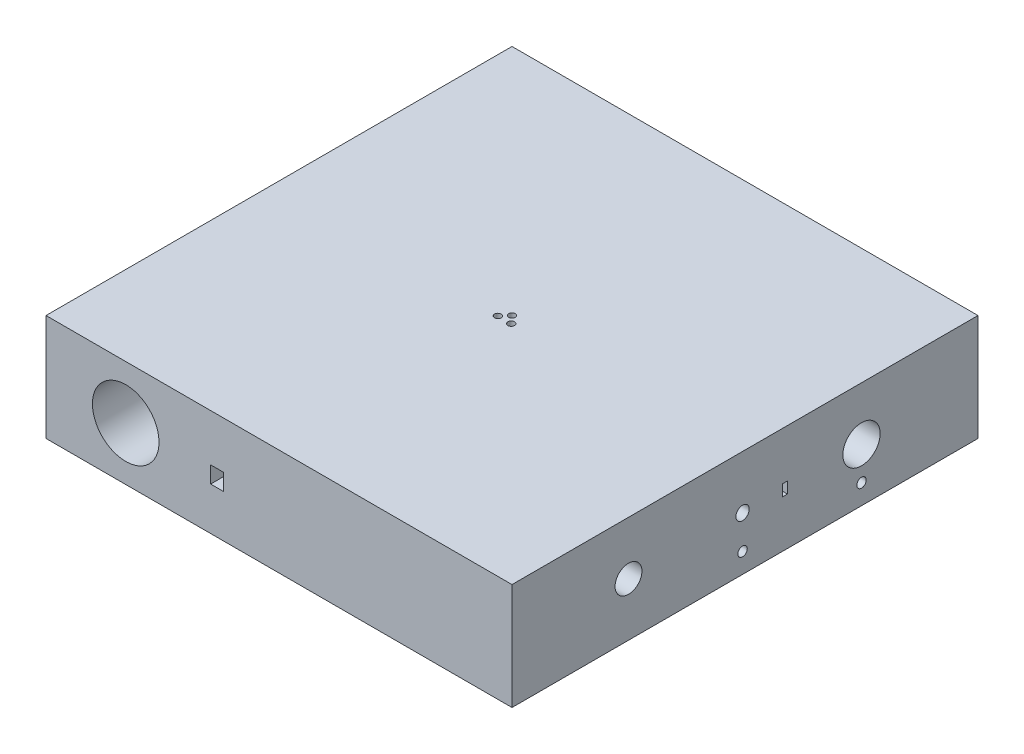
SolidWorks part; units mm, degrees
ref_plane "Front Plane" through (0, 0, 0) normal (0, 0, 1) x (1, 0, 0)
ref_plane "Top Plane" through (0, 0, 0) normal (0, 1, 0) x (1, 0, 0)
ref_plane "Right Plane" through (0, 0, 0) normal (1, 0, 0) x (0, 0, -1)
sketch "Sketch1" plane through (0, 0, 0) normal (0, 1, 0) x (1, 0, 0)
  line L1 (-175, 175) -> (175, 175)
  line L2 (-175, 175) -> (-175, -175)
  line L3 (-175, -175) -> (175, -175)
  line L4 (175, 175) -> (175, -175)
  line L5 (-175, 175) -> (175, -175) construction
  line L6 (-175, -175) -> (175, 175) construction
  point P0 (0, 0)
  dimension "D1" = 350
  dimension "D2" = 350
extrude "Boss-Extrude1" add sketch "Sketch1" along normal blind 80
sketch "Sketch2" plane through (0, 80, 0) normal (0, 1, 0) x (1, 0, 0)
  line L0 (0, 0) -> (0, 175)
  line L1 (175, 175) -> (-175, 175) construction
  line L2 (175, -175) -> (175, 175) construction
  circle A0 centre (0, 0) radius 2.5
  circle A1 centre (5, -5.5902) radius 2.5
  circle A2 centre (-5, -5.5902) radius 2.5
  point P7 (175, 0)
  point P12 (7.2907, -6.8733)
  point P13 (8.972, -8.4717)
  point P14 (0, 0)
  point P15 (-9.9071, -1.3596)
  point P16 (-5.5157, -5.1491)
  point P17 (0, 0)
  dimension "D1" = 5
  dimension "D5" = 5
  dimension "D6" = 5
  dimension "D9" = 170
  dimension "D2" = 175
  dimension "D3" = 175
  dimension "D4" = 7.5
  dimension "D7" = 7.5
  dimension "D8" = 10
extrude "Cut-Extrude1" cut sketch "Sketch2" against normal through all contours A0 region at (-1.7178, 80, 1.7178)
extrude "Cut-Extrude2" cut sketch "Sketch2<4>" against normal through all contours A1 region at (5, 80, 5.5902)
sketch "Sketch2<4>" plane through (0, 80, 0) normal (0, 1, 0) x (1, 0, 0) same geometry as "Sketch2"
extrude "Cut-Extrude3" cut sketch "Sketch2<5>" against normal through all contours A2 region at (-5, 80, 5.5902)
sketch "Sketch2<5>" plane through (0, 80, 0) normal (0, 1, 0) x (1, 0, 0) same geometry as "Sketch2"
sketch "Sketch3" plane through (-175, 0, 0) normal (-1, 0, 0) x (0, 0, 1)
  line L0 (-175, 80) -> (-175, 0) construction
  line L1 (-28.15, 35.4316) -> (-31.85, 35.4316)
  line L2 (-28.15, 35.4316) -> (-28.15, 43.9316)
  line L3 (-28.15, 43.9316) -> (-31.85, 43.9316)
  line L4 (-31.85, 35.4316) -> (-31.85, 43.9316)
  line L5 (-28.15, 35.4316) -> (-31.85, 43.9316) construction
  line L6 (-28.15, 43.9316) -> (-31.85, 35.4316) construction
  point P0 (-30, 39.6816)
  point P7 (-175, 40)
  dimension "D1" = 8.5
  dimension "D2" = 3.7
  dimension "D3" = 145
extrude "Cut-Extrude4" cut sketch "Sketch3" against normal through all
sketch "Sketch4" plane through (-175, 0, 0) normal (-1, 0, 0) x (0, 0, 1)
  line L0 (175, 80) -> (175, 0) construction
  line L3 (-175, 0) -> (175, 0) construction
  circle A0 centre (87.5, 40) radius 10.1
  dimension "D1" = 20.2
  dimension "D2" = 87.5
  dimension "D3" = 40
extrude "Cut-Extrude5" cut sketch "Sketch4" against normal through all
sketch "Sketch6" plane through (-175, 0, 0) normal (-1, 0, 0) x (0, 0, 1)
  line L0 (-28.15, 35.4316) -> (-28.15, 43.9316) construction
  line L1 (-175, 0) -> (175, 0) construction
  circle A0 centre (1.85, 15) radius 3.555
  point P5 (-28.15, 39.6816)
  dimension "D1" = 7.11
  dimension "D2" = 30
  dimension "D3" = 15
extrude "Cut-Extrude7" cut sketch "Sketch6" against normal through all and the other way blind 10
sketch "Sketch7" plane through (-175, 0, 0) normal (-1, 0, 0) x (0, 0, 1)
  line L0 (-175, 80) -> (-175, 0) construction
  line L1 (-175, 0) -> (175, 0) construction
  circle A0 centre (-87.5, 15) radius 3.555
  dimension "D1" = 7.11
  dimension "D2" = 87.5
  dimension "D3" = 15
extrude "Cut-Extrude8" cut sketch "Sketch7" against normal through all
sketch "Sketch9" plane through (-175, 0, 0) normal (-1, 0, 0) x (0, 0, 1)
  line L0 (-175, 80) -> (-175, 0) construction
  line L1 (-175, 0) -> (175, 0) construction
  circle A0 centre (-87.5, 40) radius 14
  dimension "D1" = 28
  dimension "D2" = 87.5
  dimension "D3" = 40
extrude "Cut-Extrude10" cut sketch "Sketch9" against normal through all
sketch "Sketch11" plane through (-175, 0, 0) normal (-1, 0, 0) x (0, 0, 1)
  line L3 (-28.15, 35.4316) -> (-28.15, 43.9316) construction
  line L4 (-175, 0) -> (175, 0) construction
  circle A0 centre (1.85, 40) radius 5.025
  dimension "D1" = 10.05
  dimension "D2" = 30
  dimension "D3" = 40
extrude "Cut-Extrude12" cut sketch "Sketch11" against normal through all
sketch "Sketch13" plane through (0, 0, -175) normal (0, 0, -1) x (-1, 0, 0)
  line L0 (-175, 0) -> (175, 0) construction
  circle A0 centre (115.112, 40) radius 25
  dimension "D1" = 50
  dimension "D2" = 40
extrude "Cut-Extrude14" cut sketch "Sketch13" against normal through all
sketch "Sketch14" plane through (0, 0, -175) normal (0, 0, -1) x (-1, 0, 0)
  line L1 (51.3298, 32.1941) -> (41.6298, 32.1941)
  line L2 (51.3298, 32.1941) -> (51.3298, 44.6941)
  line L3 (51.3298, 44.6941) -> (41.6298, 44.6941)
  line L4 (41.6298, 32.1941) -> (41.6298, 44.6941)
  line L5 (51.3298, 32.1941) -> (41.6298, 44.6941) construction
  line L6 (51.3298, 44.6941) -> (41.6298, 32.1941) construction
  point P0 (46.4798, 38.4441)
  dimension "D1" = 9.7
  dimension "D2" = 12.5
extrude "Cut-Extrude18" cut sketch "Sketch14" against normal through all
